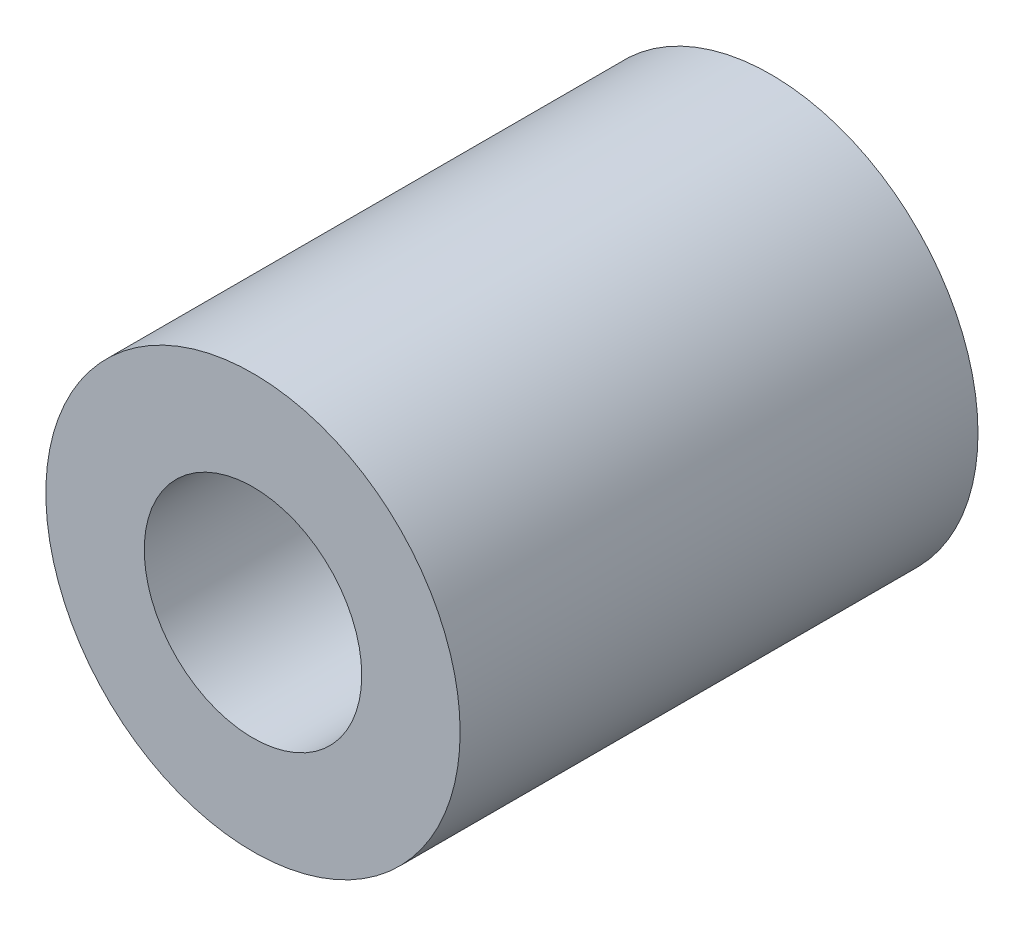
SolidWorks part; units mm, degrees
material "ABS"
ref_plane "Front Plane" through (0, 0, 0) normal (0, 0, 1) x (1, 0, 0)
ref_plane "Top Plane" through (0, 0, 0) normal (0, 1, 0) x (1, 0, 0)
ref_plane "Right Plane" through (0, 0, 0) normal (1, 0, 0) x (0, 0, -1)
sketch "Sketch1" plane through (0, 0, 0) normal (0, 0, 1) x (1, 0, 0)
  line L0 (0, 2.1) -> (0, 4) construction
  line L1 (0, -2.1) -> (0, -4) construction
  circle A0 centre (0, 0) radius 4
  circle A1 centre (0, 0) radius 2.1
  dimension "OD" = 8
  dimension "ID" = 4.2
sketch "Sketch2" plane through (0, 0, 0) normal (1, 0, 0) x (0, 0, -1)
  line L0 (-5, 2.1) -> (5, 2.1) construction
  line L1 (-5, -2.1) -> (5, -2.1) construction
  line L2 (-5, -4) -> (5, -4) construction
  line L3 (-5, 4) -> (5, 4) construction
  dimension "Length" = 10
extrude "Extrude1" add sketch "Sketch1" along normal up to vertex (5 mm away) and the other way up to vertex (5 mm away) up to point (0, 2.1, 5) other way up to point (0, 2.1, -5)
sketch "Sketch3" plane through (0, 0, 5) normal (0, 0, 1) x (1, 0, 0)
  circle A0 centre (0, 0) radius 2.1 construction
  circle A3 centre (0, 0) radius 2.1
  point P3 (-2.1, 0)
